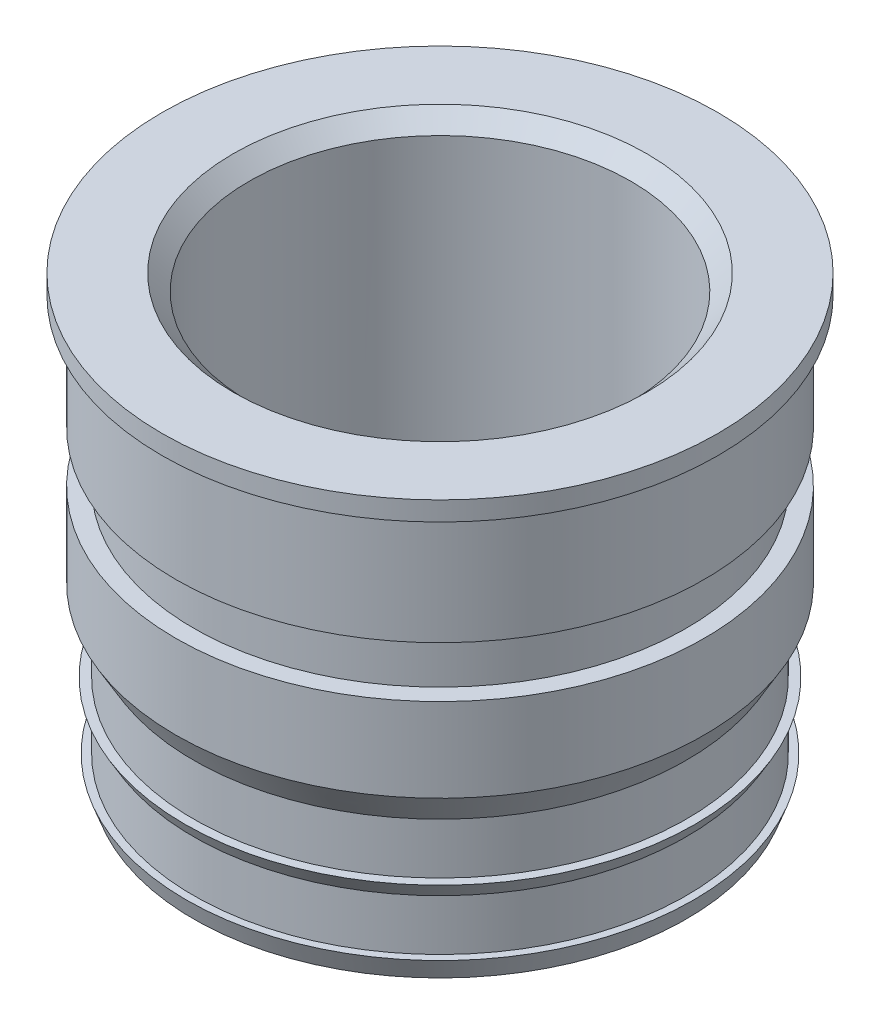
SolidWorks part; units mm, degrees
ref_plane "Front Plane" through (0, 0, 0) normal (0, 0, 1) x (1, 0, 0)
ref_plane "Top Plane" through (0, 0, 0) normal (0, 1, 0) x (1, 0, 0)
ref_plane "Right Plane" through (0, 0, 0) normal (1, 0, 0) x (0, 0, -1)
sketch "Sketch1" plane through (0, 0, 0) normal (1, 0, 0) x (0, 0, -1)
  line L0 (0, -1.715) -> (0, 1.715) construction
  line L1 (2.185, 1.715) -> (-2.185, 1.715) construction
  line L2 (-1.995, -1.715) -> (1.995, -1.715) construction
  line L3 (-1.5541, 2.1838) -> (-1.5541, 1.6838) construction
  line L4 (-1.5541, 1.6838) -> (-1.1211, 1.9338) construction
  line L5 (-1.1211, 1.9338) -> (-1.5541, 2.1838) construction
  line L6 (-1.5541, 1.9338) -> (-1.5, 1.9338) construction
  line L7 (-1.5271, 1.6994) -> (-1.5271, 2.1681) construction
  line L8 (-1.1752, 1.9338) -> (-1.1211, 1.9338) construction
  line L9 (-1.6906, -1.715) -> (-1.9304, 1.715)
  line L10 (-1.5, 2.1525) -> (-1.5, 1.715) construction
  line L11 (1.6906, -1.715) -> (1.9304, 1.715)
  line L12 (-1.1752, 1.9025) -> (-1.1752, 1.965) construction
  point P6 (0, -2.725)
  point P8 (-1.5, 1.715)
  point P9 (1.5, 1.715)
  point P16 (-1.5271, 1.9338)
  dimension "Installed Length" = 3.43
  dimension "Thread Size" = 3
  dimension "For Minimum Material Thickness" = 4.44
  dimension "Diameter" = 4.37
  dimension "Thread Pitch" = 0.5
  dimension "D1" = 0.0625
  dimension "C" = 3.99
  dimension "For Hole Taper Angle" = 8
  dimension "For Maximum Hole Diameter" = 3.8608
sketch "Sketch2" plane through (0, 0, 0) normal (1, 0, 0) x (0, 0, -1)
  line L0 (-1.5, 1.715) -> (-1.5, -1.715)
  line L1 (-1.995, -1.715) -> (1.995, -1.715) construction
  line L2 (-1.5, -1.715) -> (-1.9369, -1.715)
  line L3 (-1.9369, -1.715) -> (-1.995, -1.5554)
  line L4 (-1.995, -1.5554) -> (-1.9369, -1.5554)
  line L5 (-1.9369, -1.5554) -> (-1.9369, -1.1549)
  line L7 (-2.0757, -0.3936) -> (-2.0757, 0.2649)
  line L8 (-2.0757, 0.2649) -> (-1.9369, 0.2649)
  line L9 (-1.9369, 0.2649) -> (-1.9369, 0.6654)
  line L10 (-1.9369, 0.6654) -> (-2.0757, 0.6654)
  line L11 (-2.0757, 0.6654) -> (-2.0757, 1.4886)
  line L14 (-1.8425, 1.5641) -> (-2.185, 1.5641)
  line L15 (-2.185, 1.5641) -> (-2.185, 1.715)
  line L16 (-2.185, 1.715) -> (-1.5, 1.715)
  line L17 (-1.995, -1.5554) -> (-1.995, -1.715) construction
  line L18 (0, -1.715) -> (0, 1.715) construction
  line L19 (0, -1.715) -> (0, 1.715) construction
  line L20 (-1.9369, -1.1549) -> (-2.0063, -1.0346)
  line L21 (-2.0063, -1.0346) -> (-1.9369, -1.0346)
  line L22 (-1.9369, -1.0346) -> (-1.9369, -0.6341)
  line L23 (-2.0757, -0.3936) -> (-1.9369, -0.6341)
  line L25 (-1.8425, 1.715) -> (-1.8425, 1.6395) construction
  line L26 (-1.8425, 1.4886) -> (-2.0757, 1.4886)
  line L27 (-1.9369, -1.5554) -> (-1.9369, -1.715) construction
  line L28 (-1.8425, 1.5641) -> (-1.8425, 1.4886)
  line L29 (-1.8425, 1.6395) -> (-1.8425, 1.5641) construction
  line L30 (-2.0063, -1.0346) -> (-2.0063, -0.5139) construction
  dimension "D1" = 20
  dimension "D2" = 30
  dimension "D3" = 3.8738
  dimension "D4" = 0.1509
  dimension "D5" = 4.1515
  dimension "D6" = 0.8232
  dimension "D7" = 4.0126
  dimension "D8" = 0.6586
revolve "Revolve1" add sketch "Sketch2" angle 360 about L0
cosmetic thread "Cosmetic Thread1" parameters "D1"=3.5934, "D2"=4
cosmetic thread "Cosmetic Thread2" parameters "D1"=0.8232, "D2"=3.1515
cosmetic thread "Cosmetic Thread3" parameters "D1"=0.8347, "D2"=3.1515
chamfer "Chamfer1" distance 0.125 angle 45 2 edges at (0, -1.715, -1.5) (0, 1.715, -1.5)
ref_axis "Center Axis 1" through (0, -1.715, 0) along (0, 1, 0)
sketch "Sketch3" plane through (0, 1.715, 0) normal (0, 1, 0) x (1, 0, 0)
  circle A0 centre (0, 0) radius 1.5
curve "Helix/Spiral1" [suppressed] pitch 0.5 height 3.93 turns 7.86
sketch "Sketch4" plane through (0, 0, 0) normal (1, 0, 0) x (0, 0, -1)
  line L0 (-1.5271, 2.1681) -> (-1.5271, 1.6994)
  line L1 (-1.5271, 1.6994) -> (-1.1752, 1.9025)
  line L2 (-1.1752, 1.9025) -> (-1.1752, 1.965)
  line L3 (-1.1752, 1.965) -> (-1.5271, 2.1681)
sweep "Sweep1" [suppressed] add profiles "Sketch4" path "Helix/Spiral1"
sketch "Sketch5" plane through (0, 1.715, 0) normal (0, 1, 0) x (1, 0, 0)
  line L0 (-1.149, 1.149) -> (1.149, -1.149) construction
  line L2 (-1.149, -1.149) -> (1.149, 1.149) construction
  circle A0 centre (0, 0) radius 1.625 construction
  circle A1 centre (0, 0) radius 1.625
extrude "Cut-Extrude1" [suppressed] cut sketch "Sketch5" against normal through all both draft 45 and the other way through all
sketch "Sketch6" plane through (0, -1.715, 0) normal (0, -1, 0) x (1, 0, 0)
  circle A0 centre (0, 0) radius 1.625 construction
  circle A1 centre (0, 0) radius 1.625
extrude "Cut-Extrude2" [suppressed] cut sketch "Sketch6" against normal through all both draft 45 and the other way through all
sketch "Sketch7" plane through (0, 1.4886, 0) normal (0, 1, 0) x (1, 0, 0)
  circle A0 centre (0, 0) radius 2.0757 construction
  circle A1 centre (0, 0) radius 2.0757
curve "Helix/Spiral2" [suppressed] pitch 34.3 height 0.8232 turns 0.024
sketch "Sketch8" plane through (0, 1.4886, 0) normal (0, 1, 0) x (1, 0, 0)
  line L0 (0, -2.0757) -> (0, -1.8425) construction
  line L1 (0, -1.9591) -> (0.1811, -2.0678)
  line L2 (0, -1.9591) -> (-0.1811, -2.0678)
  line L3 (-0.1811, -2.0757) -> (0.1811, -2.0757) construction
  circle A2 centre (0, 0) radius 1.8425 construction
  circle A3 centre (0, 0) radius 2.0757 construction
  circle A4 centre (0, 0) radius 1.8425 construction
  arc A5 (-0.1811, -2.0678) -> (0.1811, -2.0678) centre (0, 0) ccw
  dimension "D1" = 0.3623
sweep "Cut-Sweep1" [suppressed] cut profiles "Sketch8" path "Helix/Spiral2"
sketch "Sketch9" plane through (0, 0.2649, 0) normal (0, 1, 0) x (1, 0, 0)
  circle A0 centre (0, 0) radius 2.0757 construction
  circle A1 centre (0, 0) radius 2.0757
curve "Helix/Spiral3" [suppressed] pitch 34.3 height 0.8232 turns 0.024
sketch "Sketch10" plane through (0, 0.2649, 0) normal (0, 1, 0) x (1, 0, 0)
  line L2 (0.1811, -2.0678) -> (0, -1.9591)
  line L3 (0, -1.9591) -> (-0.1811, -2.0678)
  line L4 (0.1811, -2.0678) -> (0, -1.9591)
  line L5 (0, -1.9591) -> (-0.1811, -2.0678)
  arc A1 (-0.1811, -2.0678) -> (0.1811, -2.0678) centre (0, 0) ccw
  arc A2 (-0.1811, -2.0678) -> (0.1811, -2.0678) centre (0, 0) ccw
  dimension "D1" = 0
sweep "Cut-Sweep2" [suppressed] cut profiles "Sketch10" path "Helix/Spiral3"
pattern_circular "CirPattern1" [suppressed] count 36 over 360 about axis through (0, -1.715, 0) along (0, 1, 0) reverse direction yes of bodies 109
equation "\"D1@Sketch1\"=\"Thread Pitch@Sketch1\"/8"
equation "\"D3@Sketch2\"=\"C@Sketch1\"/1.03"
equation "\"D5@Sketch2\"=.95*\"Diameter@Sketch1\""
equation "\"D4@Sketch2\"=.044*\"Installed Length@Sketch1\""
equation "\"D6@Sketch2\"=.24*\"Installed Length@Sketch1\""
equation "\"D1@Chamfer1\"=.25*\"Thread Pitch@Sketch1\""
equation "\"D3@Helix/Spiral1\"=\"Installed Length@Sketch1\"+\"Thread Pitch@Sketch1\""
equation "\"D4@Helix/Spiral1\"=\"Thread Pitch@Sketch1\""
equation "\"D3@Helix/Spiral2\"=\"D6@Sketch2\""
equation "\"D4@Helix/Spiral2\"=\"Installed Length@Sketch1\"*10"
equation "\"D1@Sketch8\"=(.95*\"Diameter@Sketch1\"*PI)/36"
equation "\"D3@Helix/Spiral3\"=\"D6@Sketch2\""
equation "\"D4@Helix/Spiral3\"=\"Installed Length@Sketch1\"*10"
equation "\"D8@Sketch2\"=\"D6@Sketch2\"*.8"
